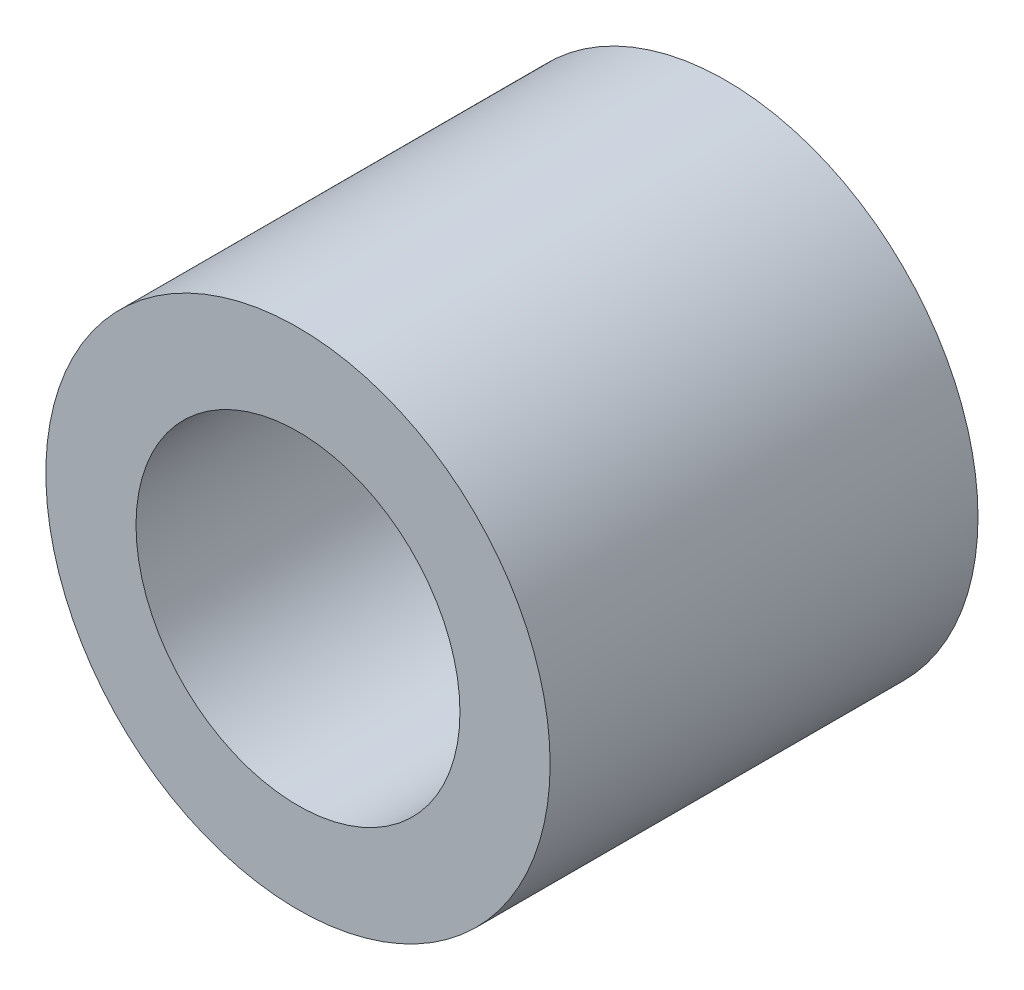
SolidWorks part; units mm, degrees
ref_plane "Top Plane" through (0, 0, 0) normal (0, 0, 1) x (1, 0, 0)
ref_plane "Right Plane" through (0, 0, 0) normal (0, 1, 0) x (1, 0, 0)
ref_plane "Front Plane" through (0, 0, 0) normal (1, 0, 0) x (0, 0, -1)
ref_axis "x-axis" through (-88.99, 0, 0) along (1, 0, 0)
ref_axis "y-axis" through (0, -55, 0) along (0, 1, 0)
ref_axis "z-axis" through (0, 0, 55) along (0, 0, -1)
sketch "Sketch1" plane through (0, 0, 0) normal (0, 0, 1) x (1, 0, 0)
  circle A0 centre (0, 0) radius 4.125
  dimension "D1" = 8.25
extrude "Boss-Extrude1" add sketch "Sketch1" along normal blind 7
hole_wizard "M5 Clearance Hole1" positions "Sketch2" profile "Sketch3" hole size "M5" standard "ANSI Metric" end condition through all
sketch "Sketch2" plane through (0, 0, 7) normal (0, 0, 1) x (1, 0, 0)
  point P0 (0, 0)
sketch "Sketch3" plane through (0, 0, 7) normal (1, 0, 0) x (0, -1, 0)
  line L0 (0, 0) -> (0, 7)
  line L1 (0, 7) -> (2.65, 7)
  line L2 (2.65, 7) -> (2.65, 0)
  line L5 (2.65, 0) -> (0, 0)
  line L11 (0, -6.35) -> (0, 107.95) construction
  dimension "Thru Hole Dia." = 5.3
  dimension "Thru Hole Depth" = 7
